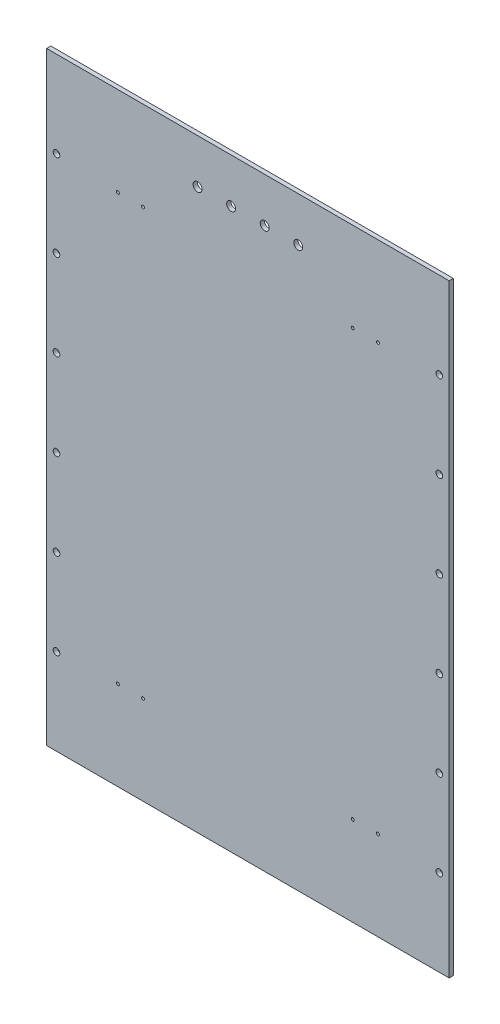
SolidWorks part; units mm, degrees
material "Plain Carbon Steel"
ref_plane "Front Plane" through (0, 0, 0) normal (0, 0, 1) x (1, 0, 0)
ref_plane "Top Plane" through (0, 0, 0) normal (0, 1, 0) x (1, 0, 0)
ref_plane "Right Plane" through (0, 0, 0) normal (1, 0, 0) x (0, 0, -1)
sketch "Sketch1" plane through (0, 0, 0) normal (0, 0, 1) x (1, 0, 0)
  line L1 (-304.8, -457.2) -> (304.8, -457.2)
  line L2 (-304.8, -457.2) -> (-304.8, 457.2)
  line L3 (-304.8, 457.2) -> (304.8, 457.2)
  line L4 (304.8, -457.2) -> (304.8, 457.2)
  line L5 (-304.8, -457.2) -> (304.8, 457.2) construction
  line L6 (-304.8, 457.2) -> (304.8, -457.2) construction
  point P0 (0, 0)
  dimension "D1" = 914.4
  dimension "D2" = 609.6
extrude "Boss-Extrude1" add sketch "Sketch1" along normal mid plane 6.35
sketch "Sketch2" plane through (0, 0, 3.175) normal (0, 0, 1) x (1, 0, 0)
  line L0 (-304.8, -457.2) -> (304.8, -457.2) construction
  line L1 (-304.8, 457.2) -> (-304.8, -457.2) construction
  line L2 (0, 457.2) -> (0, -457.2) construction
  line L3 (304.8, 457.2) -> (-304.8, 457.2) construction
  line L4 (304.8, 0) -> (-304.8, 0) construction
  line L5 (304.8, -457.2) -> (304.8, 457.2) construction
  point P0 (-196.85, -322.2625)
  point P1 (-158.75, -322.2625)
  point P14 (196.85, -322.2625)
  point P15 (158.75, -322.2625)
  point P16 (158.75, 322.2625)
  point P17 (196.85, 322.2625)
  point P18 (-158.75, 322.2625)
  point P19 (-196.85, 322.2625)
  dimension "D1" = 134.9375
  dimension "D2" = 107.95
  dimension "D3" = 38.1
hole_wizard "#8 Clearance Hole1" positions "Sketch2" profile "Sketch3" hole size "#8" standard "ANSI Inch" end condition up to next
sketch "Sketch3" plane through (-196.85, -322.2625, 3.175) normal (1, 0, 0) x (0, -1, 0)
  line L0 (0, 0) -> (0, 6.35)
  line L1 (0, 6.35) -> (2.2479, 6.35)
  line L2 (2.2479, 6.35) -> (2.2479, 0)
  line L5 (2.2479, 0) -> (0, 0)
  line L11 (0, -6.35) -> (0, 107.95) construction
  dimension "Thru Hole Dia." = 4.4958
  dimension "Thru Hole Depth" = 6.35
sketch "Sketch4" plane through (0, 0, 3.175) normal (0, 0, 1) x (1, 0, 0)
  circle A0 centre (76.2, 389.8926) radius 6.7462
  circle A1 centre (76.2, 389.8926) radius 6.7462 construction
  circle A2 centre (-25.4, 389.8926) radius 6.7462 construction
  circle A3 centre (25.4, 389.8926) radius 6.7462 construction
  circle A4 centre (-76.2, 389.8926) radius 6.7462 construction
  circle A5 centre (-25.4, 389.8926) radius 6.7462
  circle A6 centre (25.4, 389.8926) radius 6.7462
  circle A7 centre (-76.2, 389.8926) radius 6.7462
extrude "Cut-Extrude1" cut sketch "Sketch4" against normal through all both and the other way through all
sketch "Sketch8" plane through (0, 0, 3.175) normal (0, 0, 1) x (1, 0, 0)
  line L0 (-304.8, 457.2) -> (-304.8, -457.2) construction
  line L1 (-304.8, -457.2) -> (304.8, -457.2) construction
  line L2 (0, 457.2) -> (0, -457.2) construction
  line L3 (304.8, 457.2) -> (-304.8, 457.2) construction
  circle A0 centre (158.75, -322.2625) radius 2.2479 construction
  point P0 (-289.8775, -326.5714)
  point P7 (-289.8775, -195.9429)
  point P8 (-289.8775, -65.3143)
  point P9 (-289.8775, 65.3143)
  point P10 (-289.8775, 195.9429)
  point P11 (-289.8775, 326.5714)
  point P17 (289.8775, 326.5714)
  point P18 (289.8775, 195.9429)
  point P19 (289.8775, 65.3143)
  point P20 (289.8775, -65.3143)
  point P21 (289.8775, -195.9429)
  point P22 (289.8775, -326.5714)
  dimension "D1" = 14.9225
  dimension "D2" = 130.6286
  dimension "D4" = 126.3196
  dimension "D3" = 6
hole_wizard "3/8 Clearance Hole1" positions "Sketch8" profile "Sketch9" hole size "3/8" standard "ANSI Inch" end condition up to next
sketch "Sketch9" plane through (-289.8775, -326.5714, 3.175) normal (1, 0, 0) x (0, -1, 0)
  line L0 (0, 0) -> (0, 6.35)
  line L1 (0, 6.35) -> (5.0419, 6.35)
  line L2 (5.0419, 6.35) -> (5.0419, 0)
  line L5 (5.0419, 0) -> (0, 0)
  line L11 (0, -6.35) -> (0, 107.95) construction
  dimension "Thru Hole Dia." = 10.0838
  dimension "Thru Hole Depth" = 6.35
